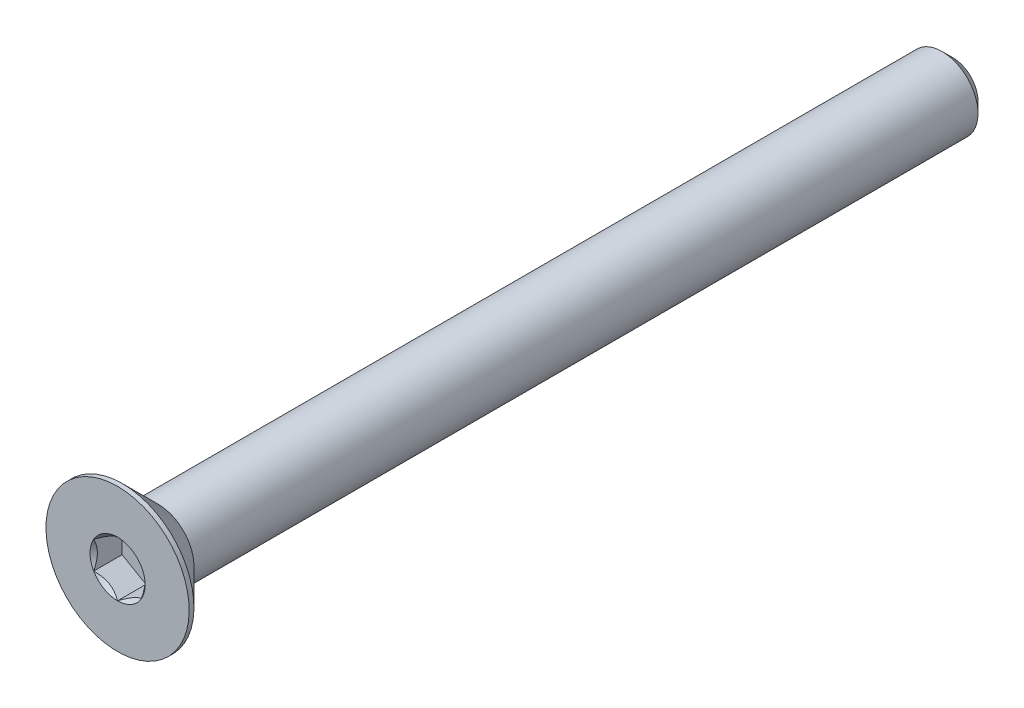
SolidWorks part; units mm, degrees
material "Alloy Steel"
ref_plane "Front" through (0, 0, 0) normal (0, 0, 1) x (1, 0, 0)
ref_plane "Top" through (0, 0, 0) normal (0, 1, 0) x (1, 0, 0)
ref_plane "Right" through (0, 0, 0) normal (1, 0, 0) x (0, 0, -1)
sketch "Sketch1" plane through (0, 0, 0) normal (1, 0, 0) x (0, 0, -1)
  line L0 (-17.5, 3) -> (-17.3, 3) construction
  line L1 (-17.3, 3) -> (-15.8, 1.5) construction
  line L2 (-17.5, 1.5) -> (17.5, 1.5) construction
  line L3 (17.5, 1.5) -> (17.5, 0) construction
  line L4 (17.5, 0) -> (-17.5, 0) construction
  line L5 (-17.5, 0) -> (-17.5, 3) construction
  line L6 (-17.5, 3) -> (-17.5, -3) construction
  line L7 (17.5, 1.5) -> (17.5, -1.5) construction
  line L8 (-17.5, -3) -> (-17.3, -3) construction
  line L9 (-17.3, -3) -> (-15.8, -1.5) construction
  line L11 (-17.5, 1.5) -> (-17.5, 0) construction
  line L12 (-15.8, 1.5) -> (-15.8, 0) construction
  line L13 (17.4688, 1.5541) -> (17.7188, 1.1211) construction
  line L14 (17.7188, 1.1211) -> (17.9688, 1.5541) construction
  line L15 (17.9688, 1.5541) -> (17.4688, 1.5541) construction
  line L16 (17.7188, 1.5541) -> (17.7188, 1.5) construction
  line L17 (17.7188, 1.5) -> (17.7188, 1.1752) construction
  line L18 (17.7188, 1.1752) -> (17.7188, 1.1211) construction
  line L19 (17.7188, 1.5271) -> (17.9531, 1.5271) construction
  line L20 (17.7188, 1.5271) -> (17.4844, 1.5271) construction
  line L21 (17.5, 1.5) -> (17.9375, 1.5) construction
  line L22 (17.6875, 1.1752) -> (17.75, 1.1752) construction
  line L23 (17.5, -1.5) -> (-15.8, -1.5) construction
  point P10 (16.25, -1.5)
  point P24 (-15.8, 1.5)
  point P30 (0, 0)
  dimension "Head Diameter" = 6
  dimension "Head Height" = 1.7
  dimension "Length" = 35
  dimension "Countersink Angle" = 90
  dimension "Thread Pitch" = 0.5
  dimension "D2" = 0.0625
  dimension "Minimum Thread Length" = 33.3
  dimension "Thread Size" = 3
  dimension "D1" = 1.25
sketch "Sketch2" plane through (0, 0, 0) normal (0, 0, 1) x (1, 0, 0)
  line L1 (0, 1.1547) -> (-1, 0.5774) construction
  line L2 (-1, 0.5774) -> (-1, -0.5774) construction
  line L3 (-1, -0.5774) -> (0, -1.1547) construction
  line L4 (0, -1.1547) -> (1, -0.5774) construction
  line L5 (1, -0.5774) -> (1, 0.5774) construction
  line L6 (1, 0.5774) -> (0, 1.1547) construction
  circle A0 centre (0, 0) radius 1 construction
  dimension "Drive Size" = 2
sketch "Sketch3" plane through (0, 0, 0) normal (1, 0, 0) x (0, 0, -1)
  line L0 (-17.5, 1.5) -> (17.5, 1.5)
  line L1 (17.5, 1.5) -> (17.5, 0)
  line L2 (17.5, 0) -> (-17.5, 0)
  line L3 (-17.5, 0) -> (-17.5, 1.5)
revolve "Revolve1" add sketch "Sketch3" angle 360 about L4
chamfer "Chamfer1" distance 0.45 angle 45 1 edges at (0, 1.5, -17.5)
sketch "Sketch6" plane through (0, 0, 0) normal (1, 0, 0) x (0, 0, -1)
  line L0 (-17.5, 3) -> (-17.3, 3)
  line L1 (-17.3, 3) -> (-15.8, 1.5)
  line L2 (-15.8, 1.5) -> (-15.8, 0)
  line L3 (-15.8, 0) -> (-17.5, 0)
  line L4 (-17.5, 0) -> (-17.5, 3)
revolve "Revolve2" add sketch "Sketch6" angle 360 about L4
sketch "Sketch8" plane through (0, 0, 17.5) normal (0, 0, 1) x (1, 0, 0)
  line L0 (0, 1.1547) -> (-1, 0.5774) construction
  line L1 (1, 0.5774) -> (0, 1.1547) construction
  line L2 (1, -0.5774) -> (1, 0.5774) construction
  line L3 (0, -1.1547) -> (1, -0.5774) construction
  line L4 (-1, 0.5774) -> (-1, -0.5774) construction
  line L5 (-1, -0.5774) -> (0, -1.1547) construction
  line L6 (0, 1.1547) -> (-1, 0.5774)
  line L7 (1, 0.5774) -> (0, 1.1547)
  line L8 (1, -0.5774) -> (1, 0.5774)
  line L9 (0, -1.1547) -> (1, -0.5774)
  line L10 (-1, 0.5774) -> (-1, -0.5774)
  line L11 (-1, -0.5774) -> (0, -1.1547)
extrude "Cut-Extrude1" cut sketch "Sketch8" against normal blind 1.19
sketch "Sketch9" plane through (0, 0, 17.5) normal (0, 0, 1) x (1, 0, 0)
  circle A0 centre (0, 0) radius 1.1547
extrude "Cut-Extrude2" cut sketch "Sketch9" against normal up to next (1.19 mm away) draft 45
ref_plane "Plane1" [suppressed] through (0, 0, 15.8) normal (0, 0, 1) x (1, 0, 0)
split "Split1" [suppressed] bodies to split 124
sketch "Sketch4" [suppressed] plane through (0, 0, -17.5) normal (0, 0, -1) x (-1, 0, 0)
  circle A0 centre (0, 0) radius 1.5 construction
  circle A1 centre (0, 0) radius 1.5
curve "Helix/Spiral1" [suppressed] pitch 0.5 height 33.8 turns 67.6
sketch "Sketch10" [suppressed] plane through (0, 0, 0) normal (1, 0, 0) x (0, 0, -1)
  line L0 (17.4844, 1.5271) -> (17.9531, 1.5271)
  line L1 (17.9531, 1.5271) -> (17.75, 1.1752)
  line L2 (17.75, 1.1752) -> (17.6875, 1.1752)
  line L3 (17.6875, 1.1752) -> (17.4844, 1.5271)
sweep "Cut-Sweep1" [suppressed] cut profiles "Sketch10" path "Helix/Spiral1"
equation "\"D2@Sketch1\" = \"Thread Pitch@Sketch1\" / 8"
equation "\"D4@Helix/Spiral1\"=\"Thread Pitch@Sketch1\""
equation "\"D3@Helix/Spiral1\"=\"Minimum Thread Length@Sketch1\"+\"Thread Pitch@Sketch1\""
equation "\"D1@Chamfer1\"=\"Thread Size@Sketch1\"*.15"
equation "\"D1@Cut-Extrude1\"=\"Head Height@Sketch1\"*.7"
equation "\"D1@Sketch1\"=\"Thread Pitch@Sketch1\"*2.5"
